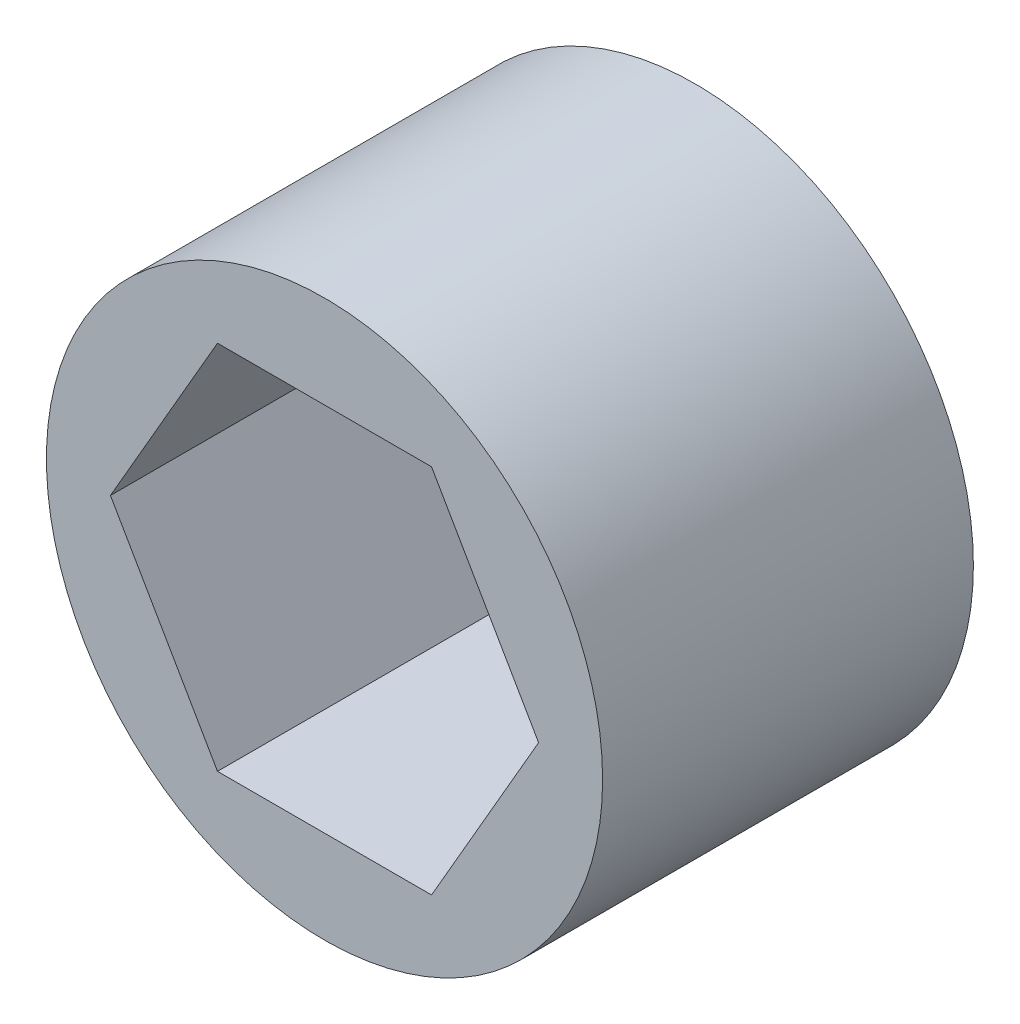
SolidWorks part; units mm, degrees
material "PET"
ref_plane "Front Plane" through (0, 0, 0) normal (0, 0, 1) x (1, 0, 0)
ref_plane "Top Plane" through (0, 0, 0) normal (0, 1, 0) x (1, 0, 0)
ref_plane "Right Plane" through (0, 0, 0) normal (1, 0, 0) x (0, 0, -1)
sketch "Sketch1" plane through (0, 0, 0) normal (0, 0, 1) x (1, 0, 0)
  line L1 (7.3323, 0) -> (3.6662, 6.35)
  line L2 (3.6662, 6.35) -> (-3.6662, 6.35)
  line L3 (-3.6662, 6.35) -> (-7.3323, 0)
  line L4 (-7.3323, 0) -> (-3.6662, -6.35)
  line L5 (-3.6662, -6.35) -> (3.6662, -6.35)
  line L6 (3.6662, -6.35) -> (7.3323, 0)
  circle A0 centre (0, 0) radius 9.525
  circle A1 centre (0, 0) radius 6.35 construction
  dimension "D1" = 12.7
  dimension "D2" = 19.05
extrude "Boss-Extrude1" add sketch "Sketch1" along normal blind 12.7
